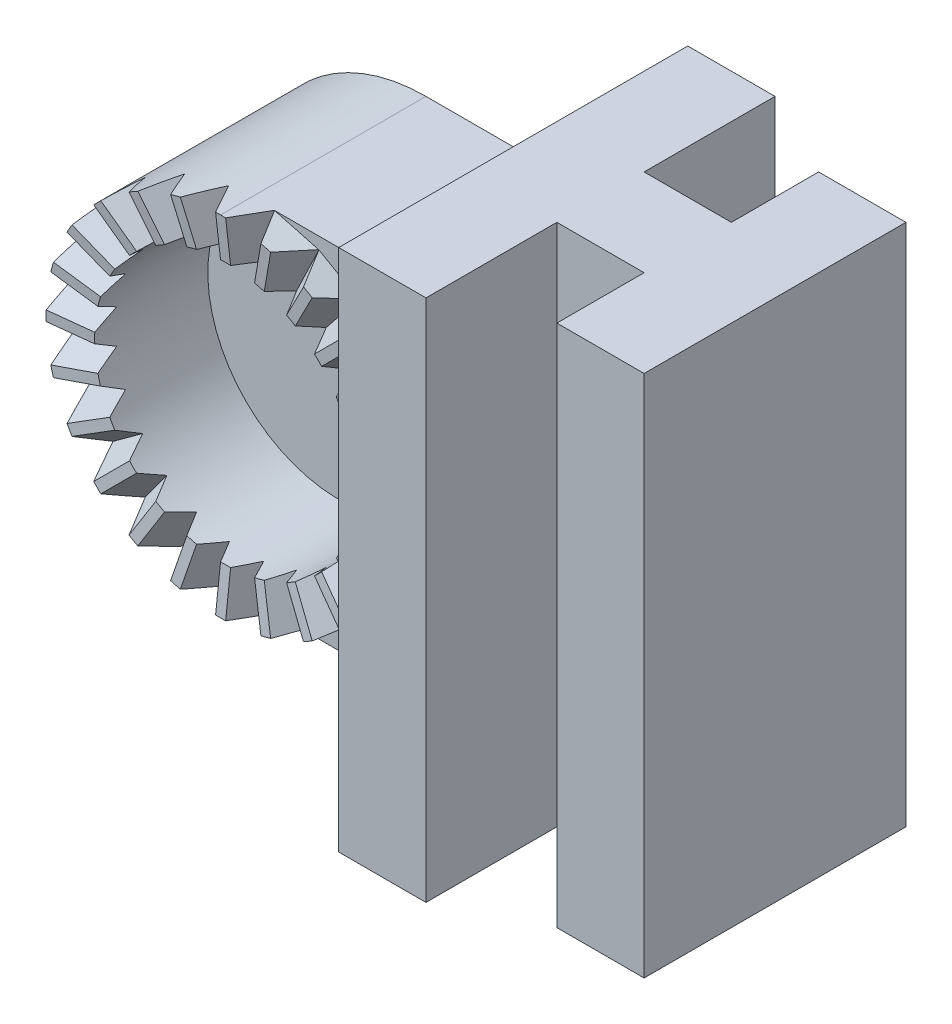
SolidWorks part; units mm, degrees
ref_plane "Front Plane" through (0, 0, 0) normal (0, 0, 1) x (1, 0, 0)
ref_plane "Top Plane" through (0, 0, 0) normal (0, 1, 0) x (1, 0, 0)
ref_plane "Right Plane" through (0, 0, 0) normal (1, 0, 0) x (0, 0, -1)
sketch "Sketch2" plane through (0, 0, 0) normal (0, 0, 1) x (1, 0, 0)
  line L0 (20, 20) -> (20, -10)
  line L1 (20, -10) -> (0, -10)
  line L2 (20, 20) -> (15, 20)
  line L3 (15, 20) -> (15, 10)
  line L4 (15, 10) -> (0, 10)
  line L5 (15, 10) -> (15, -10)
  circle A1 centre (0, 0) radius 10
  dimension "D1" = 20
  dimension "D2" = 30
  dimension "D3" = 5
  dimension "D4" = 15
extrude "Boss-Extrude1" add sketch "Sketch2" along normal blind 20 contours A1 L1 L0 L2 L3 L4 region at (17.5, 5, 0)
sketch "Sketch3" plane through (0, -10, 0) normal (0, -1, 0) x (1, 0, 0)
  line L0 (20, 12.5) -> (25, 12.5)
  line L1 (20, 20) -> (20, 0) construction
  line L2 (25, 12.5) -> (25, 17.5)
  line L3 (25, 17.5) -> (30, 17.5)
  line L4 (30, 17.5) -> (30, 2.5)
  line L5 (30, 2.5) -> (25, 2.5)
  line L6 (25, 2.5) -> (25, 7.5)
  line L7 (25, 7.5) -> (20, 7.5)
  line L8 (20, 7.5) -> (20, 12.5)
  point P4 (20, 10)
  dimension "D1" = 5
  dimension "D2" = 5
  dimension "D3" = 5
extrude "Boss-Extrude2" add sketch "Sketch3" against normal up to surface (30 mm away) up to face at (17.5, 20, 10)
extrude "Boss-Extrude3" add sketch "Sketch2<3>" along normal blind 10 contours A1 | A1 L5 L4 | A1 L1 L5 region at (11.0784, 0, 0) region at (0, 0, 0)
sketch "Sketch2<3>" plane through (0, 0, 0) normal (0, 0, 1) x (1, 0, 0) same geometry as "Sketch2"
sketch "Sketch4" plane through (0, 0, 10) normal (0, 0, 1) x (1, 0, 0)
  line L0 (0, 0) -> (-6.8443, 7.2908)
  line L2 (-8.4981, 5.271) -> (0, 0)
  circle A0 centre (0, 0) radius 7.5
  circle A1 centre (0, 0) radius 10
  arc A2 (0, 10) -> (0, -10) centre (0, 0) ccw construction
  dimension "D1" = 15
  dimension "D2" = 15
  dimension "D3" = 0
extrude "Cut-Extrude3" cut sketch "Sketch4" against normal blind 5 and the other way blind 10 contours L2 A0 L0 | L0 A0 L2 region at (-3.8576, 3.1585, 10) region at (0.1677, -0.1373, 10)
ref_plane "Plane1" through (-10, 0, 0) normal (-1, 0, 0) x (0, 0, 1)
sketch "Sketch5" plane through (-10, 0, 0) normal (-1, 0, 0) x (0, 0, 1)
  line L0 (12.267, 0) -> (10, 1.3089)
  line L1 (10, -10) -> (10, 10) construction
  line L2 (10, 1.3089) -> (10, -1.3089)
  line L3 (10, -1.3089) -> (12.267, 0)
  point P6 (10, 0)
  dimension "D1" = 60
  dimension "D2" = 2.267
ref_axis "Axis1" through (0, 0, 31.9434) along (0, 0, -1)
ref_plane "Plane2" through (-5, 0, 0) normal (-1, 0, 0) x (0, 0, 1)
sketch "Sketch6" plane through (-5, 0, 0) normal (-1, 0, 0) x (0, 0, 1)
  line L0 (10, 0.9815) -> (10, -0.9815)
  line L1 (10, 1.3089) -> (10, -1.3089) construction
  line L2 (10, -0.9815) -> (11.7, 0)
  line L3 (31.9434, 0) -> (5, 0) construction
  line L4 (11.7, 0) -> (10, 0.9815)
  dimension "D1" = 60
  dimension "D2" = 1.7
sketch3d "3DSketch1"
  line L0 (-10, 0, 12.267) -> (-5, 0, 11.7)
  line L1 (-10, -1.3089, 10) -> (-5, -0.9815, 10)
  line L2 (-10, 1.3089, 10) -> (-5, 0.9815, 10)
  line L3 (-10, 1.3089, 10) -> (-10, -1.3089, 10) construction
loft "Loft1" add profiles "Sketch5", "Sketch6" connector at (-10, 0, 12.267) connector at (-5, 0, 11.7)
pattern_circular "CirPattern5" count 24 over 360 about axis through (0, 0, 31.9434) along (0, 0, -1) of "Loft1"
extrude "Cut-Extrude4" cut sketch "Sketch4<6>" along normal blind 10 contours L0 A0 L2 | L2 A0 L0 region at (-3.8576, 3.1585, 10) region at (0.1677, -0.1373, 10)
sketch "Sketch4<6>" plane through (0, 0, 10) normal (0, 0, 1) x (1, 0, 0) same geometry as "Sketch4"
sketch "Sketch9" plane through (0, 0, 0) normal (0, 0, 1) x (1, 0, 0)
  line L0 (0, 10) -> (0, 11)
  line L1 (0, -10) -> (0, -11)
  arc A0 (0, -10) -> (0, 10) centre (0, 0) cw
  arc A1 (0, 11) -> (0, -11) centre (0, 0) ccw
  dimension "D1" = 1
extrude "Cut-Extrude5" cut sketch "Sketch9" along normal blind 20
sketch "Sketch12" plane through (0, 0, 0) normal (0, 1, 0) x (1, 0, 0)
  line L0 (-7.3585, -11.4675) -> (-10.6014, -11.8352)
  line L1 (-10, -12.267) -> (-5, -11.7) construction
  line L4 (-7.3585, -11.9675) -> (-7.3585, -11.4675)
  line L7 (-7.3585, -11.9675) -> (-10.6419, -12.3398)
  line L8 (-10.6419, -12.3398) -> (-10.6014, -11.8352)
  dimension "1" = 0.5
revolve "Cut-Revolve2" cut sketch "Sketch12" angle 360 about axis through (0, 0, 31.9434) along (0, 0, -1) region at (-8.9901, 0, 11.903)
